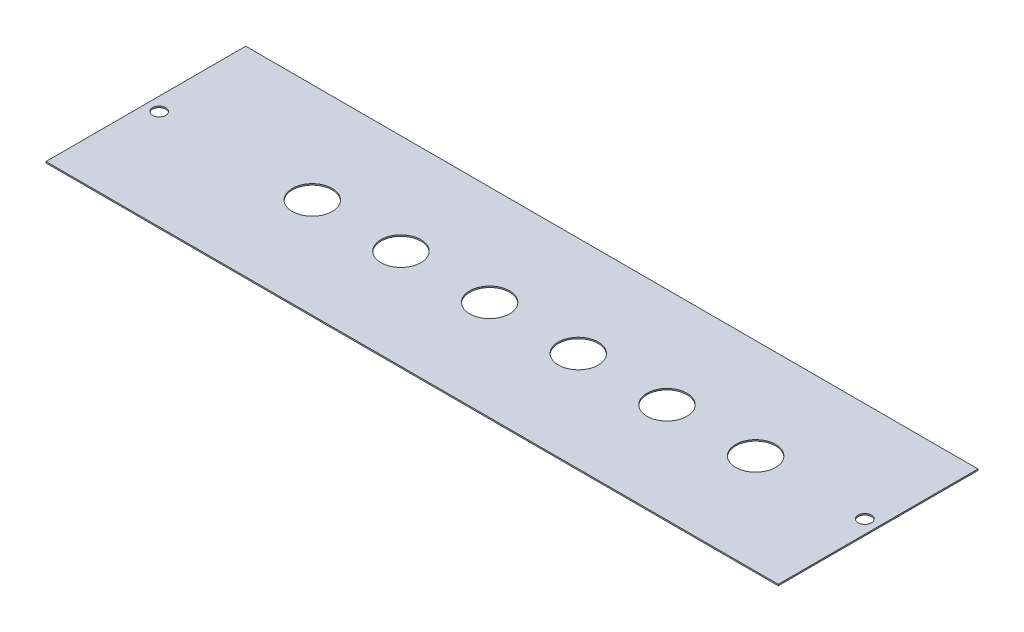
SolidWorks part; units mm, degrees
ref_plane "Front Plane" through (0, 0, 0) normal (0, 0, 1) x (1, 0, 0)
ref_plane "Top Plane" through (0, 0, 0) normal (0, 1, 0) x (1, 0, 0)
ref_plane "Right Plane" through (0, 0, 0) normal (1, 0, 0) x (0, 0, -1)
sketch "Sketch1" plane through (0, 0, 0) normal (0, 1, 0) x (1, 0, 0)
  line L1 (275, -75) -> (-275, -75)
  line L2 (275, -75) -> (275, 75)
  line L3 (275, 75) -> (-275, 75)
  line L4 (-275, -75) -> (-275, 75)
  line L5 (275, -75) -> (-275, 75) construction
  line L6 (275, 75) -> (-275, -75) construction
  point P0 (0, 0)
  dimension "D1" = 550
  dimension "D2" = 150
sheet metal parameters "Sheet-Metal1" thickness 1 parameters "D1"=1
base flange "Base-Flange1" sketch "Sketch1" thickness 1 reverse thickness direction no parameters "D1"=1
sketch "Sketch3" plane through (0, 0, 0) normal (0, 1, 0) x (1, 0, 0)
  circle A0 centre (-265, 0) radius 5
  circle A1 centre (265, 0) radius 5
  dimension "D1" = 10
  dimension "D2" = 10
  dimension "D3" = 530
  dimension "D4" = 265
extrude "Cut-Extrude1" cut sketch "Sketch3" against normal blind 1 normal cut yes
sketch "Sketch4" plane through (0, -1, 0) normal (0, -1, 0) x (1, 0, 0)
  circle A0 centre (-150, 0) radius 15
  dimension "D1" = 30
  dimension "D2" = 150
extrude "Cut-Extrude2" cut sketch "Sketch4" against normal blind 1 normal cut yes
pattern_linear "LPattern1" count 6 spacing 66.6 along (1, 0, 0) of "Cut-Extrude2"
flat pattern "Flat-Pattern1" [suppressed]
sketch "Bend-Lines1" plane through (0, 0, 0) normal (0, 1, 0) x (-1, 0, 0)
equation "\"D4@Sketch3\" = \"D3@Sketch3\" / 2"
